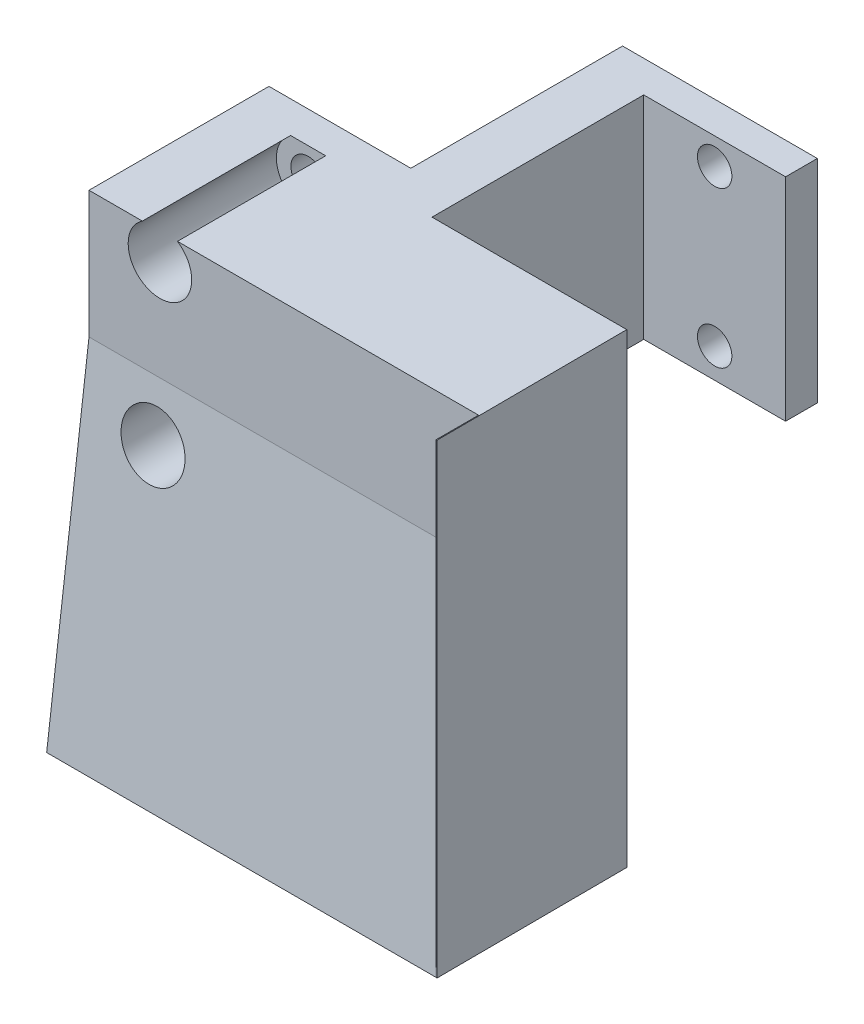
SolidWorks part; units mm, degrees
ref_plane "Front Plane" through (0, 0, 0) normal (0, 0, 1) x (1, 0, 0)
ref_plane "Top Plane" through (0, 0, 0) normal (0, 1, 0) x (1, 0, 0)
ref_plane "Right Plane" through (0, 0, 0) normal (1, 0, 0) x (0, 0, -1)
sketch "Sketch1" plane through (0, 0, 0) normal (0, 1, 0) x (1, 0, 0)
  line L0 (0, 0) -> (18.4, 0)
  line L1 (18.4, 0) -> (18.4, 20)
  line L2 (18.4, 20) -> (31.8, 20)
  line L3 (31.8, 20) -> (31.8, 23)
  line L4 (31.8, 23) -> (13.4, 23)
  line L5 (13.4, 23) -> (13.4, 3)
  line L6 (13.4, 3) -> (0, 3)
  line L7 (0, 3) -> (0, 0)
  dimension "D1" = 13.4
  dimension "D2" = 5
  dimension "D3" = 3
  dimension "D4" = 17
extrude "Boss-Extrude1" add sketch "Sketch1" along normal blind 20
sketch "Sketch2" plane through (0, 0, -20) normal (0, 0, 1) x (1, 0, 0)
  line L0 (25.1, 20) -> (25.1, 0) construction
  line L2 (18.4, 20) -> (31.8, 20) construction
  line L4 (18.4, 0) -> (31.8, 0) construction
  circle A0 centre (25.1, 17.5) radius 1.625
  circle A1 centre (25.1, 2.8) radius 1.625
  point P10 (0, 0)
  point P11 (0, 0)
  dimension "D1" = 3.25
  dimension "D2" = 2.5
  dimension "D3" = 14.7
extrude "Cut-Extrude1" cut sketch "Sketch2" against normal through all both and the other way through all
ref_plane "Plane1" through (15.9, 0, 0) normal (-1, 0, 0) x (0, 0, 1)
mirror "Mirror1" about plane through (15.9, 0, 0) normal (-1, 0, 0) of "Cut-Extrude1"
sketch "Sketch5" plane through (0, 0, 0) normal (-1, 0, 0) x (0, 0, 1)
  line L0 (0, 20) -> (0, -24)
  line L1 (0, -24) -> (18, -24)
  line L2 (18, -24) -> (14, 8)
  line L3 (14, 8) -> (14, 20)
  line L4 (14, 20) -> (0, 20)
  line L5 (-3, 0) -> (0, 0) construction
  line L6 (8, -9) -> (8, -19) construction
  line L7 (10.55, -9) -> (10.55, -19)
  line L8 (5.45, -9) -> (5.45, -19)
  arc A0 (10.55, -9) -> (5.45, -9) centre (8, -9) ccw
  arc A1 (5.45, -19) -> (10.55, -19) centre (8, -19) ccw
  point P11 (8, -14)
  dimension "D1" = 12
  dimension "D2" = 14
  dimension "D3" = 18
  dimension "D4" = 24
  dimension "D5" = 10
  dimension "D6" = 5.1
  dimension "D7" = 5
  dimension "D8" = 8
extrude "Boss-Extrude2" add sketch "Sketch5" against normal offset from surface (36.8 mm away) 5 up to face at (31.8, 10, -21.5) offset beyond the face yes
sketch "Sketch6" plane through (0, -24, 0) normal (0, -1, 0) x (1, 0, 0)
  line L0 (36.8, 0) -> (36.8858, 18)
  line L1 (36.8, 18) -> (0, 18) construction
  line L2 (36.8858, 18) -> (36.8, 18)
  line L3 (36.8, 18) -> (36.8, 0)
  dimension "D1" = 0.273
extrude "Boss-Extrude3" add sketch "Sketch6" against normal up to surface (44 mm away) up to face at (20.08, 20, -6.4)
sketch "Sketch7" plane through (0, 0, 0) normal (-1, 0, 0) x (0, 0, 1)
  line L0 (14, -24) -> (14, -9)
  line L1 (0, -24) -> (18, -24) construction
  line L2 (2, -9) -> (2, -24)
  line L3 (2, -24) -> (14, -24)
  arc A0 (14, -9) -> (2, -9) centre (8, -9) ccw
  arc A1 (10.55, -9) -> (5.45, -9) centre (8, -9) ccw construction
  dimension "D1" = 12
extrude "Cut-Extrude4" cut sketch "Sketch7" against normal offset from surface (31.8095 mm away) 5 up to face at (36.8429, -2, 9)
sketch "Sketch8" plane through (0, 0, 0) normal (0, 0, -1) x (-1, 0, 0)
  circle A0 centre (-6.7, 2.8) radius 3
  circle A1 centre (-6.7, 17.5) radius 3
  dimension "D1" = 6
extrude "Cut-Extrude5" cut sketch "Sketch8" against normal through all
